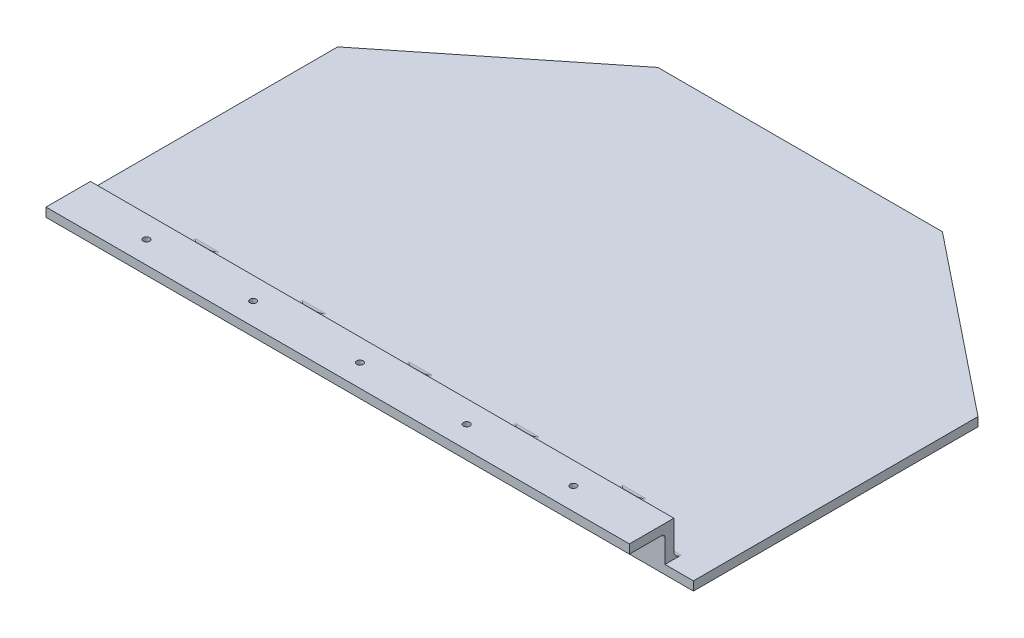
SolidWorks part; units mm, degrees
ref_plane "Front Plane" through (0, 0, 0) normal (0, 0, 1) x (1, 0, 0)
ref_plane "Top Plane" through (0, 0, 0) normal (0, 1, 0) x (1, 0, 0)
ref_plane "Right Plane" through (0, 0, 0) normal (1, 0, 0) x (0, 0, -1)
sketch "Sketch1" plane through (0, 0, 0) normal (0, 1, 0) x (1, 0, 0)
  line L0 (-114.3, 0) -> (114.3, 0)
  line L1 (-114.3, 0) -> (-114.3, 101.6)
  line L2 (0, 0) -> (0, 50000) construction
  line L3 (-114.3, 101.6) -> (-50.8, 152.4)
  line L4 (-50.8, 152.4) -> (50.8, 152.4)
  line L5 (114.3, 101.6) -> (50.8, 152.4)
  line L6 (114.3, 0) -> (114.3, 101.6)
  point P4 (0, 0)
  point P10 (0, 152.4)
  dimension "D1" = 228.6
  dimension "D2" = 101.6
  dimension "D3" = 152.4
  dimension "D4" = 101.6
extrude "Boss-Extrude1" add sketch "Sketch1" along normal blind 3.175
sketch "Sketch2" plane through (114.3, 0, 0) normal (1, 0, 0) x (0, 0, -1)
  line L0 (3.175, 3.175) -> (3.175, 15.875)
  line L1 (0, 3.175) -> (101.6, 3.175) construction
  line L2 (3.175, 15.875) -> (-12.7, 15.875)
  line L3 (-12.7, 15.875) -> (-12.7, 12.7)
  line L4 (-12.7, 12.7) -> (0, 12.7)
  line L5 (0, 12.7) -> (0, 3.175)
  line L6 (0, 3.175) -> (3.175, 3.175)
  line L7 (0, 0) -> (101.6, 0) construction
  point P11 (-12.7, 14.2875)
  dimension "D1" = 3.175
  dimension "D2" = 3.175
  dimension "D3" = 12.7
  dimension "D4" = 12.7
extrude "Boss-Extrude2" add sketch "Sketch2" against normal up to surface (228.6 mm away) up to face at (-114.3, 1.5875, -50.8)
sketch "Sketch3" plane through (0, 0, 0) normal (1, 0, 0) x (0, 0, -1)
  line L0 (3.175, 15.875) -> (15.875, 3.175)
  line L1 (3.175, 3.175) -> (101.6, 3.175) construction
  line L2 (15.875, 3.175) -> (3.175, 3.175)
  line L3 (3.175, 3.175) -> (3.175, 15.875)
  dimension "D1" = 12.7
extrude "Boss-Extrude3" add sketch "Sketch3" along normal mid plane 3.175
pattern_linear "LPattern1" count 3 spacing 38.1 along (-1, 0, 0) count 3 spacing 38.1 along (1, 0, 0) of "Boss-Extrude3"
sketch "Sketch4" plane through (0, 15.875, 0) normal (0, 1, 0) x (1, 0, 0)
  line L0 (0, 3.175) -> (0, -12.7) construction
  line L1 (1.5875, 3.175) -> (-1.5875, 3.175) construction
  line L2 (-114.3, -12.7) -> (114.3, -12.7) construction
  circle A0 centre (0, -4.7625) radius 1.143
  dimension "D1" = 2.286
extrude "Cut-Extrude1" cut sketch "Sketch4" against normal through all
pattern_linear "LPattern2" count 3 spacing 38.1 along (1, 0, 0) count 3 spacing 38.1 along (-1, 0, 0) of "Cut-Extrude1"
sketch "Sketch5" plane through (0, 0, -3.175) normal (0, 0, -1) x (-1, 0, 0)
  line L0 (-57.15, 15.875) -> (-57.15, 3.175) construction
  line L1 (-74.6125, 15.875) -> (-39.6875, 15.875) construction
  line L2 (-74.6125, 15.875) -> (-74.6125, 3.175) construction
  line L3 (-74.6125, 3.175) -> (-39.6875, 3.175) construction
  line L4 (-39.6875, 15.875) -> (-39.6875, 3.175) construction
  line L5 (-36.5125, 9.525) -> (-1.5875, 9.525) construction
  line L6 (-74.6125, 9.525) -> (-39.6875, 9.525) construction
  line L7 (-36.5125, 15.875) -> (-36.5125, 3.175) construction
  line L8 (-1.5875, 15.875) -> (-1.5875, 3.175) construction
  line L9 (-114.3, 0) -> (-50.8, 0) construction
  circle A0 centre (-57.15, 8.382) radius 1.143
  point P18 (-19.05, 9.525)
  point P19 (-55.4803, 7.5239)
  point P20 (0, 0)
  dimension "D1" = 2.286
  dimension "D2" = 38.1171
  dimension "D3" = 8.382
extrude "Cut-Extrude3" cut sketch "Sketch5" against normal through all
pattern_linear "LPattern3" count 4 spacing 38.1 along (-1, 0, 0) of "Cut-Extrude3"
sketch "Sketch6" plane through (0, 15.875, 0) normal (0, 1, 0) x (1, 0, 0)
  line L0 (114.3, 3.175) -> (104.14, 3.175)
  line L1 (77.7875, 3.175) -> (114.3, 3.175) construction
  line L2 (104.14, 3.175) -> (104.14, -12.7)
  line L3 (-114.3, -12.7) -> (114.3, -12.7) construction
  line L4 (104.14, -12.7) -> (114.3, -12.7)
  line L5 (114.3, -12.7) -> (114.3, 3.175)
  line L6 (0, 152.4) -> (0, 50152.4) construction
  line L7 (50.8, 152.4) -> (-50.8, 152.4) construction
  line L8 (-114.3, -12.7) -> (-114.3, 3.175)
  line L9 (-104.14, -12.7) -> (-114.3, -12.7)
  line L10 (-104.14, 3.175) -> (-104.14, -12.7)
  line L11 (-114.3, 3.175) -> (-104.14, 3.175)
  point P14 (0, 152.4)
  dimension "D1" = 10.16
extrude "Cut-Extrude4" cut sketch "Sketch6" against normal up to surface (12.7 mm away) up to face at (0, 3.175, -27.1096)
fillet "Fillet1" radius 2.54 31 edges at (-77.7875, 9.525, -3.175) (-90.9638, 3.175, -3.175) (-77.7875, 3.175, -9.525) (-74.6125, 9.525, -3.175) (-74.6125, 3.175, -9.525) (-57.15, 3.175, -3.175) (-39.6875, 9.525, -3.175) (-39.6875, 3.175, -9.525) (-36.5125, 9.525, -3.175) (-36.5125, 3.175, -9.525) (-19.05, 3.175, -3.175) (-1.5875, 9.525, -3.175) (-1.5875, 3.175, -9.525) (1.5875, 9.525, -3.175) (1.5875, 3.175, -9.525) (19.05, 3.175, -3.175) (36.5125, 3.175, -9.525) (36.5125, 9.525, -3.175) (74.6125, 9.525, -3.175) (74.6125, 3.175, -9.525) (39.6875, 3.175, -9.525) (39.6875, 9.525, -3.175) (77.7875, 3.175, -9.525) (77.7875, 9.525, -3.175) (90.9638, 3.175, -3.175) (57.15, 3.175, -3.175) (-76.2, 3.175, -15.875) (-38.1, 3.175, -15.875) (0, 3.175, -15.875) (38.1, 3.175, -15.875) (76.2, 3.175, -15.875)
fillet "Fillet2" radius 1.27 1 edges at (0, 12.7, 0)
